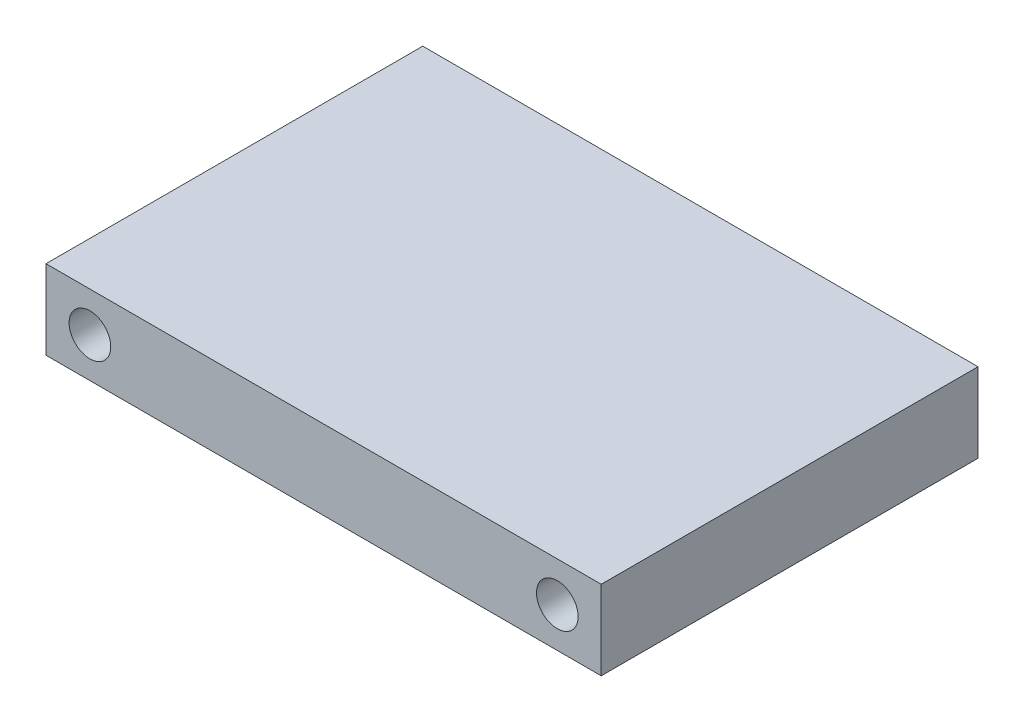
SolidWorks part; units mm, degrees
ref_plane "Спереди" through (0, 0, 0) normal (0, 0, 1) x (1, 0, 0)
ref_plane "Сверху" through (0, 0, 0) normal (0, 1, 0) x (1, 0, 0)
ref_plane "Справа" through (0, 0, 0) normal (1, 0, 0) x (0, 0, -1)
sketch "Эскиз1" plane through (0, 0, 0) normal (0, 0, 1) x (1, 0, 0)
  line L1 (0, 0) -> (56, 0)
  line L2 (0, 0) -> (0, 8)
  line L3 (0, 8) -> (56, 8)
  line L4 (56, 0) -> (56, 8)
  dimension "D1" = 56
  dimension "D2" = 8
extrude "Бобышка-Вытянуть1" add sketch "Эскиз1" along normal blind 38
sketch "Эскиз2" plane through (0, 0, 38) normal (0, 0, 1) x (1, 0, 0)
  line L0 (0, 8) -> (0, 0) construction
  line L1 (56, 8) -> (0, 8) construction
  circle A0 centre (4.43, 4) radius 2.1
  circle A1 centre (51.57, 4) radius 2.1
  point P4 (0, 4)
  point P7 (28, 8)
  dimension "D1" = 4.2
  dimension "D2" = 0
  dimension "D3" = 23.57
  dimension "D4" = 2
extrude "Вырез-Вытянуть1" cut sketch "Эскиз2" against normal through all
